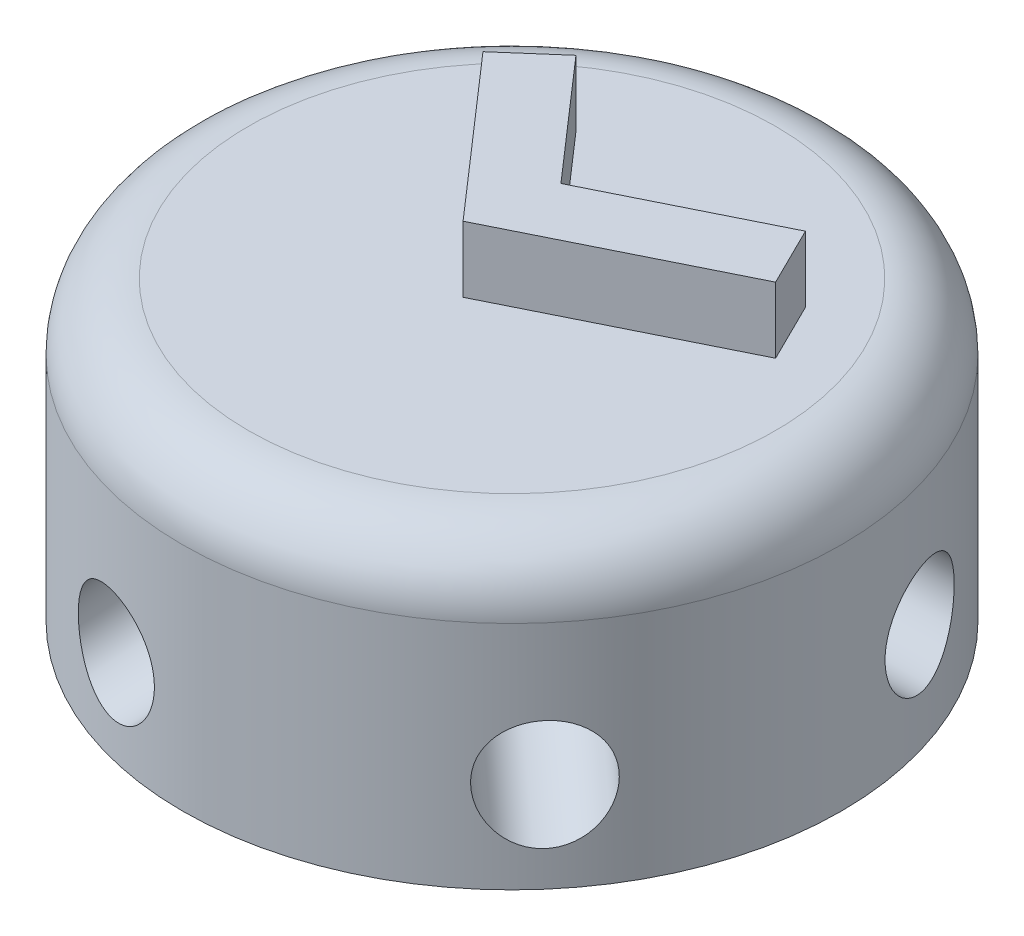
SolidWorks part; units mm, degrees
ref_plane "Front Plane" through (0, 0, 0) normal (0, 0, 1) x (1, 0, 0)
ref_plane "Top Plane" through (0, 0, 0) normal (0, 1, 0) x (1, 0, 0)
ref_plane "Right Plane" through (0, 0, 0) normal (1, 0, 0) x (0, 0, -1)
sketch "Sketch1" plane through (0, 0, 0) normal (0, 1, 0) x (1, 0, 0)
  circle A0 centre (0, 0) radius 10
  dimension "D1" = 20
extrude "base" add sketch "Sketch1" along normal blind 3 and the other way blind 6
ref_axis "6hubaxis" through (0, 5.5, 0) along (0, -1, 0)
ref_plane "Plane1" through (2.6705, -1.0931, 2.7701) normal (-0.6676, 0.2733, -0.6925) x (-0.6559, 0.2243, 0.7208)
sketch "Sketch2" [suppressed] plane through (2.6705, -1.0931, 2.7701) normal (-0.6676, 0.2733, -0.6925) x (-0.6559, 0.2243, 0.7208)
  circle A0 centre (0, 0) radius 1.5 construction
  circle A1 centre (0, 0) radius 1.5
extrude "hole1" [suppressed] cut sketch "Sketch2" against normal through all
pattern_circular "hole1mirror" [suppressed] count 2 over 360 about axis through (0, 5.5, 0) along (0, -1, 0) of bodies 112
ref_plane "Plane2" through (-0.9417, -1.2361, 3.6858) normal (0.2354, 0.309, -0.9215) x (-0.9719, 0.0738, -0.2235)
sketch "Sketch3" plane through (-0.9417, -1.2361, 3.6858) normal (0.2354, 0.309, -0.9215) x (-0.9719, 0.0738, -0.2235)
  circle A0 centre (0, 0) radius 1.5 construction
  circle A1 centre (0, 0) radius 1.5 construction
  circle A2 centre (0, 0) radius 1.6
  dimension "D1" = 3.2
extrude "hole2" cut sketch "Sketch3" against normal through all
pattern_circular "hole2mirror" count 2 over 360 about axis through (0, 5.5, 0) along (0, -1, 0) of "hole2"
ref_plane "Plane3" through (-3.7178, -1.2361, 0.8061) normal (0.9295, 0.309, -0.2015) x (-0.1912, -0.0636, -0.9795)
sketch "Sketch4" plane through (-3.7178, -1.2361, 0.8061) normal (0.9295, 0.309, -0.2015) x (-0.1912, -0.0636, -0.9795)
  circle A0 centre (0, 0) radius 1.5 construction
  circle A1 centre (0, 0) radius 1.5 construction
  circle A2 centre (0, 0) radius 1.6
  dimension "D1" = 3.2
extrude "hole3" cut sketch "Sketch4" against normal through all
pattern_circular "hole3mirror" [suppressed] count 2 over 360 about axis through (0, 5.5, 0) along (0, -1, 0) of bodies 117
ref_plane "Plane4" through (3.672, -1.0931, -1.1497) normal (-0.918, 0.2733, 0.2874) x (0.2755, -0.082, 0.9578)
sketch "Sketch5" plane through (3.672, -1.0931, -1.1497) normal (-0.918, 0.2733, 0.2874) x (0.2755, -0.082, 0.9578)
  circle A0 centre (0, 0) radius 1.5 construction
  circle A1 centre (0, 0) radius 1.5 construction
  circle A2 centre (0, 0) radius 1.6
  dimension "D1" = 3.2
extrude "Cut-Extrude1" cut sketch "Sketch5" against normal through all
ref_plane "Plane5" through (2.8756, -1.2361, 2.4906) normal (-0.7189, 0.309, -0.6227) x (-0.572, 0.2459, 0.7825)
sketch "Sketch6" plane through (2.8756, -1.2361, 2.4906) normal (-0.7189, 0.309, -0.6227) x (-0.572, 0.2459, 0.7825)
  circle A0 centre (0, 0) radius 1.5 construction
  circle A1 centre (0, 0) radius 1.5 construction
  circle A2 centre (0, 0) radius 1.6
  dimension "D1" = 3.2
extrude "Cut-Extrude2" cut sketch "Sketch6" against normal through all
ref_plane "Plane6" through (-2.6705, -1.0931, -2.7701) normal (0.6676, 0.2733, 0.6925) x (0.7445, -0.2451, -0.621)
sketch "Sketch7" plane through (-2.6705, -1.0931, -2.7701) normal (0.6676, 0.2733, 0.6925) x (0.7445, -0.2451, -0.621)
  circle A0 centre (0, 0) radius 1.5 construction
  circle A1 centre (0, 0) radius 1.5 construction
  circle A2 centre (0, 0) radius 1.6
  dimension "D1" = 3.2
extrude "Cut-Extrude3" cut sketch "Sketch7" against normal through all
sketch "Sketch8" plane through (0, -6, 0) normal (0, -1, 0) x (1, 0, 0)
  circle A0 centre (0, 0) radius 5
extrude "Boss-Extrude1" [suppressed] add sketch "Sketch8" along normal blind 2
fillet "Fillet1" radius 2 1 edges at (0, 3, 10)
sketch "Sketch9" plane through (0, 3, 0) normal (0, 1, 0) x (1, 0, 0)
  line L0 (0, 0) -> (5.6543, 2.7985)
  line L1 (0, 0) -> (-3.6468, 4.1765)
extrude "Extrude-Thin1" add sketch "Sketch9" along normal blind 2 thin thin type mid plane wall 2
